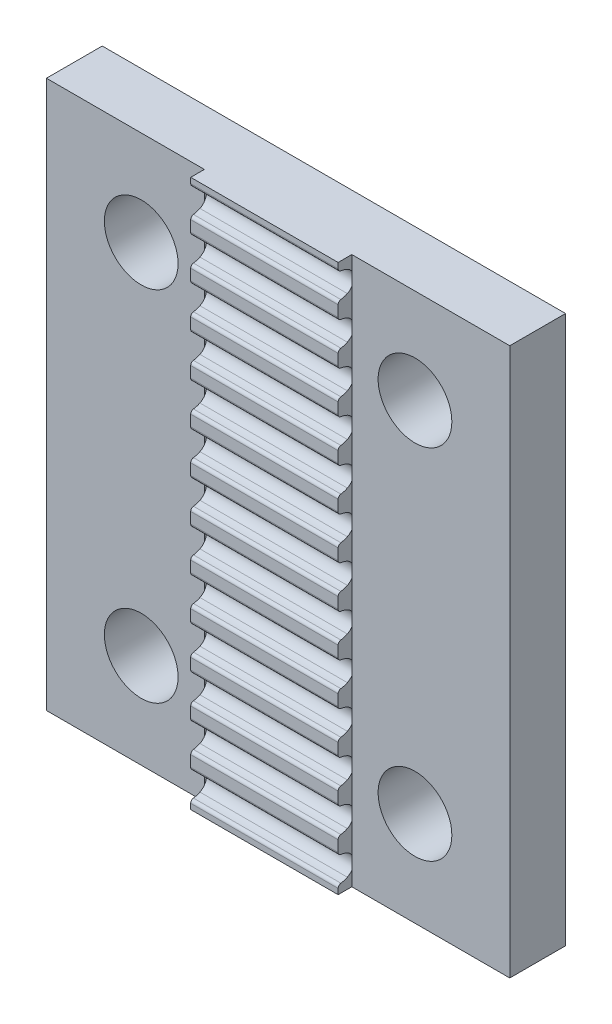
SolidWorks part; units mm, degrees
ref_plane "Piano frontale" through (0, 0, 0) normal (0, 0, 1) x (1, 0, 0)
ref_plane "Piano superiore" through (0, 0, 0) normal (0, 1, 0) x (1, 0, 0)
ref_plane "Piano destro" through (0, 0, 0) normal (1, 0, 0) x (0, 0, -1)
sketch "Schizzo1" plane through (0, 0, 0) normal (0, 0, 1) x (1, 0, 0)
  line L1 (-11, -13) -> (11, -13)
  line L2 (-11, -13) -> (-11, 13)
  line L3 (-11, 13) -> (11, 13)
  line L4 (11, -13) -> (11, 13)
  line L5 (-11, -13) -> (11, 13) construction
  line L6 (-11, 13) -> (11, -13) construction
  line L7 (-6.5, 8.5) -> (6.5, 8.5) construction
  line L8 (-6.5, 8.5) -> (-6.5, -8.5) construction
  line L9 (-6.5, -8.5) -> (6.5, -8.5) construction
  line L10 (6.5, 8.5) -> (6.5, -8.5) construction
  line L11 (-6.5, 8.5) -> (6.5, -8.5) construction
  line L12 (-6.5, -8.5) -> (6.5, 8.5) construction
  line L13 (-3.5, 13) -> (3.5, 13)
  line L14 (-3.5, 13) -> (-3.5, -13)
  line L15 (-3.5, -13) -> (3.5, -13)
  line L16 (3.5, 13) -> (3.5, -13)
  line L17 (-3.5, 13) -> (3.5, -13) construction
  line L18 (-3.5, -13) -> (3.5, 13) construction
  circle A0 centre (-6.5, 8.5) radius 1.75
  circle A1 centre (6.5, 8.5) radius 1.75
  circle A2 centre (6.5, -8.5) radius 1.75
  circle A3 centre (-6.5, -8.5) radius 1.75
  point P0 (0, 0)
  point P6 (0, 0)
  point P7 (0, 0)
  point P15 (0, 0)
  point P20 (0, 0)
  dimension "D3" = 3.5
  dimension "D1" = 22
  dimension "D2" = 26
  dimension "D5" = 7
  dimension "D6" = 4.5
  dimension "D7" = 4.5
extrude "Estrusione-Estrusione1" add sketch "Schizzo1" along normal blind 1 contours L14 L3 L2 L1 A3 A0 | L16 L3 L14 L1 | L3 L16 L1 L4 A2 A1 region at (-7.3321, 0, 0) region at (0, 0, 0) region at (7.3321, 0, 0)
extrude "Estrusione-Estrusione2" add sketch "Schizzo1<3>" along normal blind 1.65 contours L14 L15 L16 L13
sketch "Schizzo1<3>" plane through (0, 0, 0) normal (0, 0, 1) x (1, 0, 0) same geometry as "Schizzo1"
extrude "Estrusione-Estrusione3" add sketch "Schizzo1<5>" against normal blind 1.65 contours L14 L3 L2 L1 A3 A0 | L16 L3 L14 L1 | L3 L16 L1 L4 A2 A1 region at (-7.3321, 0, 0) region at (0, 0, 0) region at (7.3321, 0, 0)
sketch "Schizzo1<5>" plane through (0, 0, 0) normal (0, 0, 1) x (1, 0, 0) same geometry as "Schizzo1"
sketch "Schizzo2" plane through (-3.5, 0, 0) normal (-1, 0, 0) x (0, 0, 1)
  line L0 (1.65, 13) -> (1.65, 12.7402)
  line L2 (1.65, 13) -> (1, 13) construction
  line L3 (1.65, 13) -> (1, 13) construction
  line L4 (1.65, 11) -> (1.65, 10.7402)
  line L5 (2.28, 11) -> (2.28, 9)
  line L6 (1.65, 9) -> (1.65, 9.2598)
  line L7 (1.65, 13) -> (1.65, -13) construction
  line L8 (1.65, 13) -> (1.65, -13) construction
  line L9 (0.9, 12) -> (2.28, 12) construction
  line L10 (2.28, 13) -> (2.28, 11)
  line L11 (1.65, 11) -> (1.65, 11.2598)
  line L12 (1.65, 11) -> (1, 11) construction
  line L13 (0.9, 10) -> (2.28, 10) construction
  line L14 (1.65, 9) -> (1.65, 8.7402)
  line L15 (2.28, 9) -> (2.28, 7)
  line L16 (1.65, 7) -> (1.65, 7.2598)
  line L17 (1.65, 9) -> (1, 9) construction
  line L18 (0.9, 8) -> (2.28, 8) construction
  line L19 (1.65, 7) -> (1.65, 6.7402)
  line L20 (2.28, 7) -> (2.28, 5)
  line L21 (1.65, 5) -> (1.65, 5.2598)
  line L22 (1.65, 7) -> (1, 7) construction
  line L23 (0.9, 6) -> (2.28, 6) construction
  line L24 (1.65, 5) -> (1.65, 4.7402)
  line L25 (2.28, 5) -> (2.28, 3)
  line L26 (1.65, 3) -> (1.65, 3.2598)
  line L27 (1.65, 5) -> (1, 5) construction
  line L28 (0.9, 4) -> (2.28, 4) construction
  line L29 (1.65, 3) -> (1.65, 2.7402)
  line L30 (2.28, 3) -> (2.28, 1)
  line L31 (1.65, 1) -> (1.65, 1.2598)
  line L32 (1.65, 3) -> (1, 3) construction
  line L33 (0.9, 2) -> (2.28, 2) construction
  line L34 (1.65, 1) -> (1.65, 0.7402)
  line L35 (2.28, 1) -> (2.28, -1)
  line L36 (1.65, -1) -> (1.65, -0.7402)
  line L37 (1.65, 1) -> (1, 1) construction
  line L38 (0.9, 0) -> (2.28, 0) construction
  line L39 (1.65, -1) -> (1.65, -1.2598)
  line L40 (2.28, -1) -> (2.28, -3)
  line L41 (1.65, -3) -> (1.65, -2.7402)
  line L42 (1.65, -1) -> (1, -1) construction
  line L43 (0.9, -2) -> (2.28, -2) construction
  line L44 (1.65, -3) -> (1.65, -3.2598)
  line L45 (2.28, -3) -> (2.28, -5)
  line L46 (1.65, -5) -> (1.65, -4.7402)
  line L47 (1.65, -3) -> (1, -3) construction
  line L48 (0.9, -4) -> (2.28, -4) construction
  line L49 (1.65, -5) -> (1.65, -5.2598)
  line L50 (2.28, -5) -> (2.28, -7)
  line L51 (1.65, -7) -> (1.65, -6.7402)
  line L52 (1.65, -5) -> (1, -5) construction
  line L53 (0.9, -6) -> (2.28, -6) construction
  line L54 (1.65, -7) -> (1.65, -7.2598)
  line L55 (2.28, -7) -> (2.28, -9)
  line L56 (1.65, -9) -> (1.65, -8.7402)
  line L57 (1.65, -7) -> (1, -7) construction
  line L58 (0.9, -8) -> (2.28, -8) construction
  line L59 (1.65, -9) -> (1.65, -9.2598)
  line L60 (2.28, -9) -> (2.28, -11)
  line L61 (1.65, -11) -> (1.65, -10.7402)
  line L62 (1.65, -9) -> (1, -9) construction
  line L63 (0.9, -10) -> (2.28, -10) construction
  line L64 (1.65, -11) -> (1.65, -11.2598)
  line L65 (2.28, -11) -> (2.28, -13)
  line L66 (1.65, -13) -> (1.65, -12.7402)
  line L67 (1.65, -11) -> (1, -11) construction
  line L68 (0.9, -12) -> (2.28, -12) construction
  line L69 (1.65, -13) -> (2.28, -13)
  line L70 (2.28, 13) -> (1.65, 13)
  arc A0 (1.65, 12.7402) -> (1.5196, 12.5915) centre (1.5, 12.7402) cw
  arc A1 (1.2118, 12.4989) -> (1.5196, 12.5915) centre (1.65, 11.6) cw
  arc A2 (1.65, 10.7402) -> (1.5196, 10.5915) centre (1.5, 10.7402) cw
  arc A3 (1.2118, 10.4989) -> (1.5196, 10.5915) centre (1.65, 9.6) cw
  arc A4 (1.2118, 10.4989) -> (1.2118, 9.5011) centre (1.455, 10) ccw
  arc A5 (1.2118, 12.4989) -> (1.2118, 11.5011) centre (1.455, 12) ccw
  arc A6 (1.2118, 11.5011) -> (1.5196, 11.4085) centre (1.65, 12.4) ccw
  arc A7 (1.65, 11.2598) -> (1.5196, 11.4085) centre (1.5, 11.2598) ccw
  arc A8 (1.2118, 9.5011) -> (1.5196, 9.4085) centre (1.65, 10.4) ccw
  arc A9 (1.65, 9.2598) -> (1.5196, 9.4085) centre (1.5, 9.2598) ccw
  arc A10 (1.65, 8.7402) -> (1.5196, 8.5915) centre (1.5, 8.7402) cw
  arc A11 (1.2118, 8.4989) -> (1.5196, 8.5915) centre (1.65, 7.6) cw
  arc A12 (1.2118, 8.4989) -> (1.2118, 7.5011) centre (1.455, 8) ccw
  arc A13 (1.2118, 7.5011) -> (1.5196, 7.4085) centre (1.65, 8.4) ccw
  arc A14 (1.65, 7.2598) -> (1.5196, 7.4085) centre (1.5, 7.2598) ccw
  arc A15 (1.65, 6.7402) -> (1.5196, 6.5915) centre (1.5, 6.7402) cw
  arc A16 (1.2118, 6.4989) -> (1.5196, 6.5915) centre (1.65, 5.6) cw
  arc A17 (1.2118, 6.4989) -> (1.2118, 5.5011) centre (1.455, 6) ccw
  arc A18 (1.2118, 5.5011) -> (1.5196, 5.4085) centre (1.65, 6.4) ccw
  arc A19 (1.65, 5.2598) -> (1.5196, 5.4085) centre (1.5, 5.2598) ccw
  arc A20 (1.65, 4.7402) -> (1.5196, 4.5915) centre (1.5, 4.7402) cw
  arc A21 (1.2118, 4.4989) -> (1.5196, 4.5915) centre (1.65, 3.6) cw
  arc A22 (1.2118, 4.4989) -> (1.2118, 3.5011) centre (1.455, 4) ccw
  arc A23 (1.2118, 3.5011) -> (1.5196, 3.4085) centre (1.65, 4.4) ccw
  arc A24 (1.65, 3.2598) -> (1.5196, 3.4085) centre (1.5, 3.2598) ccw
  arc A25 (1.65, 2.7402) -> (1.5196, 2.5915) centre (1.5, 2.7402) cw
  arc A26 (1.2118, 2.4989) -> (1.5196, 2.5915) centre (1.65, 1.6) cw
  arc A27 (1.2118, 2.4989) -> (1.2118, 1.5011) centre (1.455, 2) ccw
  arc A28 (1.2118, 1.5011) -> (1.5196, 1.4085) centre (1.65, 2.4) ccw
  arc A29 (1.65, 1.2598) -> (1.5196, 1.4085) centre (1.5, 1.2598) ccw
  arc A30 (1.65, 0.7402) -> (1.5196, 0.5915) centre (1.5, 0.7402) cw
  arc A31 (1.2118, 0.4989) -> (1.5196, 0.5915) centre (1.65, -0.4) cw
  arc A32 (1.2118, 0.4989) -> (1.2118, -0.4989) centre (1.455, 0) ccw
  arc A33 (1.2118, -0.4989) -> (1.5196, -0.5915) centre (1.65, 0.4) ccw
  arc A34 (1.65, -0.7402) -> (1.5196, -0.5915) centre (1.5, -0.7402) ccw
  arc A35 (1.65, -1.2598) -> (1.5196, -1.4085) centre (1.5, -1.2598) cw
  arc A36 (1.2118, -1.5011) -> (1.5196, -1.4085) centre (1.65, -2.4) cw
  arc A37 (1.2118, -1.5011) -> (1.2118, -2.4989) centre (1.455, -2) ccw
  arc A38 (1.2118, -2.4989) -> (1.5196, -2.5915) centre (1.65, -1.6) ccw
  arc A39 (1.65, -2.7402) -> (1.5196, -2.5915) centre (1.5, -2.7402) ccw
  arc A40 (1.65, -3.2598) -> (1.5196, -3.4085) centre (1.5, -3.2598) cw
  arc A41 (1.2118, -3.5011) -> (1.5196, -3.4085) centre (1.65, -4.4) cw
  arc A42 (1.2118, -3.5011) -> (1.2118, -4.4989) centre (1.455, -4) ccw
  arc A43 (1.2118, -4.4989) -> (1.5196, -4.5915) centre (1.65, -3.6) ccw
  arc A44 (1.65, -4.7402) -> (1.5196, -4.5915) centre (1.5, -4.7402) ccw
  arc A45 (1.65, -5.2598) -> (1.5196, -5.4085) centre (1.5, -5.2598) cw
  arc A46 (1.2118, -5.5011) -> (1.5196, -5.4085) centre (1.65, -6.4) cw
  arc A47 (1.2118, -5.5011) -> (1.2118, -6.4989) centre (1.455, -6) ccw
  arc A48 (1.2118, -6.4989) -> (1.5196, -6.5915) centre (1.65, -5.6) ccw
  arc A49 (1.65, -6.7402) -> (1.5196, -6.5915) centre (1.5, -6.7402) ccw
  arc A50 (1.65, -7.2598) -> (1.5196, -7.4085) centre (1.5, -7.2598) cw
  arc A51 (1.2118, -7.5011) -> (1.5196, -7.4085) centre (1.65, -8.4) cw
  arc A52 (1.2118, -7.5011) -> (1.2118, -8.4989) centre (1.455, -8) ccw
  arc A53 (1.2118, -8.4989) -> (1.5196, -8.5915) centre (1.65, -7.6) ccw
  arc A54 (1.65, -8.7402) -> (1.5196, -8.5915) centre (1.5, -8.7402) ccw
  arc A55 (1.65, -9.2598) -> (1.5196, -9.4085) centre (1.5, -9.2598) cw
  arc A56 (1.2118, -9.5011) -> (1.5196, -9.4085) centre (1.65, -10.4) cw
  arc A57 (1.2118, -9.5011) -> (1.2118, -10.4989) centre (1.455, -10) ccw
  arc A58 (1.2118, -10.4989) -> (1.5196, -10.5915) centre (1.65, -9.6) ccw
  arc A59 (1.65, -10.7402) -> (1.5196, -10.5915) centre (1.5, -10.7402) ccw
  arc A60 (1.65, -11.2598) -> (1.5196, -11.4085) centre (1.5, -11.2598) cw
  arc A61 (1.2118, -11.5011) -> (1.5196, -11.4085) centre (1.65, -12.4) cw
  arc A62 (1.2118, -11.5011) -> (1.2118, -12.4989) centre (1.455, -12) ccw
  arc A63 (1.2118, -12.4989) -> (1.5196, -12.5915) centre (1.65, -11.6) ccw
  arc A64 (1.65, -12.7402) -> (1.5196, -12.5915) centre (1.5, -12.7402) ccw
  point P26 (1.65, 12.4)
  point P37 (1.65, 10.4)
  point P57 (1.65, 8.4)
  point P77 (1.65, 6.4)
  point P97 (1.65, 4.4)
  point P117 (1.65, 2.4)
  point P137 (1.65, 0.4)
  point P157 (1.65, -1.6)
  point P177 (1.65, -3.6)
  point P197 (1.65, -5.6)
  point P217 (1.65, -7.6)
  point P237 (1.65, -9.6)
  point P257 (1.65, -11.6)
  dimension "D2" = 1
  dimension "D3" = 0.15
  dimension "D4" = 0.75
  dimension "D5" = 1.38
  dimension "D6" = 1
  dimension "D7" = 13
  dimension "D8" = 0.63
  dimension "D9" = 0.4
extrude "Taglio-Estrusione1" cut sketch "Schizzo2" against normal up to surface (7 mm away) up to face at (3.5, 0, 1.325)
